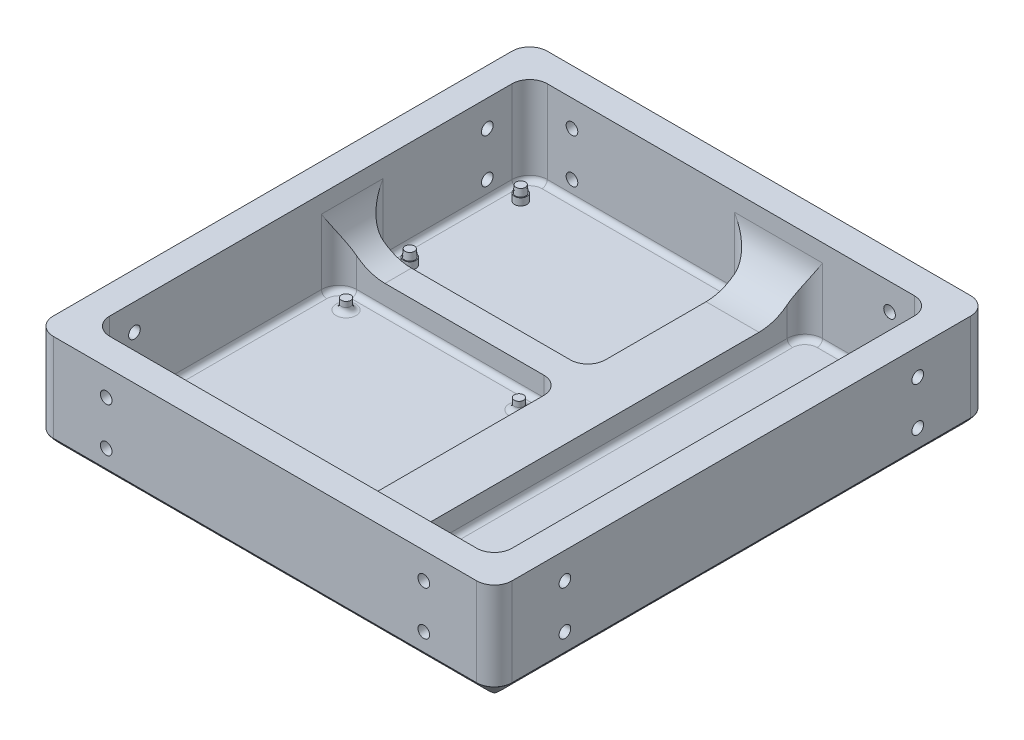
SolidWorks part; units mm, degrees
ref_plane "Front Plane" through (0, 0, 0) normal (0, 0, 1) x (1, 0, 0)
ref_plane "Top Plane" through (0, 0, 0) normal (0, 1, 0) x (1, 0, 0)
ref_plane "Right Plane" through (0, 0, 0) normal (1, 0, 0) x (0, 0, -1)
sketch "Sketch1" plane through (0, 0, 0) normal (0, 1, 0) x (1, 0, 0)
  line L1 (-83.6568, 40.258) -> (46.3432, 40.258)
  line L2 (-83.6568, 40.258) -> (-83.6568, -99.742)
  line L3 (-83.6568, -99.742) -> (46.3432, -99.742)
  line L4 (46.3432, 40.258) -> (46.3432, -99.742)
  dimension "D1" = 140
  dimension "D2" = 130
extrude "Boss-Extrude2" add sketch "Sketch1" along normal blind 10
sketch "Sketch3" plane through (0, 10, 0) normal (0, 1, 0) x (1, 0, 0)
  line L0 (-83.6568, -99.742) -> (46.3432, -99.742) construction
  line L1 (-83.6568, 40.258) -> (-83.6568, -99.742) construction
  circle A0 centre (-68.6568, -26.742) radius 1.3
  circle A1 centre (-19.6568, -26.742) radius 1.3
  circle A2 centre (-68.6568, -84.742) radius 1.3
  circle A3 centre (-19.6568, -84.742) radius 1.3
  dimension "D1" = 49
  dimension "D2" = 58
  dimension "D3" = 49
  dimension "D6" = 2.6
  dimension "D7" = 2.6
  dimension "D8" = 2.6
  dimension "D9" = 2.6
  dimension "D4" = 15
  dimension "D5" = 15
extrude "Boss-Extrude4" add sketch "Sketch3" along normal blind 2
sketch "Sketch4" plane through (0, 12, 0) normal (0, 1, 0) x (1, 0, 0)
  circle A0 centre (-68.6568, -26.742) radius 1.15
  circle A1 centre (-68.6568, -84.742) radius 1.15
  circle A2 centre (-19.6568, -84.742) radius 1.15
  circle A3 centre (-19.6568, -26.742) radius 1.15
  dimension "D1" = 2.3
  dimension "D2" = 2.3
  dimension "D3" = 2.3
  dimension "D4" = 2.3
extrude "Boss-Extrude5" add sketch "Sketch4" along normal blind 3 draft 5 draft outward yes
chamfer "Chamfer1" distance 1.5 angle 45 4 edges at (-19.6568, 15, 86.1545) (-68.6568, 15, 28.1545) (-19.6568, 15, 28.1545) (-68.6568, 15, 86.1545)
sketch "Sketch5" plane through (0, 10, 0) normal (0, 1, 0) x (1, 0, 0)
  line L0 (46.3432, 40.258) -> (-83.6568, 40.258) construction
  line L1 (-83.6568, -99.742) -> (-73.6568, -99.742)
  line L2 (-83.6568, -99.742) -> (-83.6568, 40.258)
  line L3 (-83.6568, 40.258) -> (-73.6568, 40.258)
  line L4 (-73.6568, -89.742) -> (-73.6568, 30.258)
  line L5 (46.3432, -99.742) -> (46.3432, 40.258) construction
  line L6 (46.3432, 40.258) -> (-83.6568, 40.258)
  line L7 (46.3432, 40.258) -> (46.3432, 30.258)
  line L8 (36.3432, 30.258) -> (-73.6568, 30.258)
  line L9 (-83.6568, 40.258) -> (-83.6568, 30.258)
  line L10 (-83.6568, -99.742) -> (46.3432, -99.742)
  line L11 (-83.6568, -99.742) -> (-83.6568, -89.742)
  line L12 (-73.6568, -89.742) -> (36.3432, -89.742)
  line L13 (46.3432, -99.742) -> (46.3432, -89.742)
  line L15 (46.3432, -99.742) -> (36.3432, -99.742)
  line L16 (46.3432, -99.742) -> (46.3432, 40.258)
  line L17 (46.3432, 40.258) -> (36.3432, 40.258)
  line L18 (36.3432, -89.742) -> (36.3432, 30.258)
  line M3 (-83.6568, 40.258) -> (-83.6568, -99.742)
  line M4 (-83.6568, -99.742) -> (46.3432, -99.742)
  line M5 (46.3432, -99.742) -> (46.3432, 40.258)
  line M6 (46.3432, 40.258) -> (-83.6568, 40.258)
  dimension "D1" = 10
  dimension "D2" = 10
  dimension "D3" = 10
  dimension "D4" = 10
extrude "Boss-Extrude6" add sketch "Sketch5" along normal blind 20 contours L6 L2 L10 L18 L12 L4 L8 M6 M3 M4 M5
sketch "Sketch7" plane through (0, 30, 0) normal (0, 1, 0) x (1, 0, 0)
  line L0 (46.3432, 40.258) -> (-83.6568, 40.258) construction
  line L1 (-75.6568, 32.258) -> (38.3432, 32.258)
  line L2 (-75.6568, 32.258) -> (-75.6568, -91.742)
  line L3 (-75.6568, -91.742) -> (38.3432, -91.742)
  line L4 (38.3432, 32.258) -> (38.3432, -91.742)
  line L5 (-83.6568, -99.742) -> (46.3432, -99.742) construction
  line L6 (-83.6568, 40.258) -> (-83.6568, -99.742) construction
  line L7 (46.3432, -99.742) -> (46.3432, 40.258) construction
  line L9 (-73.6568, 30.258) -> (36.3432, 30.258)
  line L10 (-73.6568, 30.258) -> (-73.6568, -89.742)
  line L11 (-73.6568, -89.742) -> (36.3432, -89.742)
  line L12 (36.3432, 30.258) -> (36.3432, -89.742)
  dimension "D1" = 8
  dimension "D2" = 8
  dimension "D3" = 8
  dimension "D4" = 8
extrude "Cut-Extrude2" cut sketch "Sketch7" against normal up to surface (20 mm away) up to face at (-18.6568, 10, 29.742)
sketch "Sketch9" plane through (0, 10, 0) normal (0, 1, 0) x (1, 0, 0)
  line L0 (38.3432, -91.742) -> (-75.6568, -91.742) construction
  line L1 (-12.6568, -91.742) -> (2.3432, -91.742)
  line L2 (-12.6568, -91.742) -> (-12.6568, 32.258)
  line L3 (-12.6568, 32.258) -> (2.3432, 32.258)
  line L4 (2.3432, -91.742) -> (2.3432, 32.258)
  line L5 (38.3432, -91.742) -> (38.3432, 32.258) construction
  line L6 (-75.6568, 32.258) -> (38.3432, 32.258) construction
  dimension "D1" = 15
  dimension "D2" = 36
  dimension "D3" = 0
extrude "Boss-Extrude8" add sketch "Sketch9" along normal blind 5
sketch "Sketch10" plane through (0, 10, 0) normal (0, 1, 0) x (1, 0, 0)
  line L0 (-75.6568, -91.742) -> (-75.6568, 32.258) construction
  line L1 (-75.6568, -21.742) -> (-12.6568, -21.742)
  line L2 (-75.6568, -21.742) -> (-75.6568, -14.242)
  line L3 (-75.6568, -14.242) -> (-12.6568, -14.242)
  line L4 (-12.6568, -21.742) -> (-12.6568, -14.242)
  line L5 (-12.6568, 32.258) -> (-12.6568, -91.742) construction
  circle A0 centre (-68.6568, -26.742) radius 1.2817 construction
  dimension "D1" = 7.5
  dimension "D2" = 5
extrude "Boss-Extrude9" add sketch "Sketch10" along normal blind 5
sketch "Sketch12" plane through (0, 10, 0) normal (0, 1, 0) x (1, 0, 0)
  line L1 (-75.6568, 32.258) -> (-12.6568, 32.258)
  line L2 (-75.6568, 32.258) -> (-75.6568, -14.242)
  line L3 (-75.6568, -14.242) -> (-12.6568, -14.242)
  line L4 (-12.6568, 32.258) -> (-12.6568, -14.242)
  line L5 (2.3432, 32.258) -> (38.3432, 32.258)
  line L6 (2.3432, 32.258) -> (2.3432, -91.742)
  line L7 (2.3432, -91.742) -> (38.3432, -91.742)
  line L8 (38.3432, 32.258) -> (38.3432, -91.742)
  line L9 (-12.6568, -91.742) -> (-75.6568, -91.742)
  line L10 (-12.6568, -91.742) -> (-12.6568, -21.742)
  line L11 (-12.6568, -21.742) -> (-75.6568, -21.742)
  line L12 (-75.6568, -91.742) -> (-75.6568, -21.742)
  circle A0 centre (-68.6846, -26.742) radius 1.3279
  circle A1 centre (-68.6568, -26.742) radius 0.0279 construction
  circle A2 centre (-19.6568, -26.7699) radius 1.3279
  circle A3 centre (-19.6568, -26.742) radius 0.0279 construction
  circle A4 centre (-19.6289, -84.742) radius 1.2539
  circle A5 centre (-19.6568, -84.742) radius 0.0279 construction
  circle A6 centre (-68.6568, -84.7141) radius 1.2539
  circle A7 centre (-68.6568, -84.742) radius 0.0279 construction
extrude "Cut-Extrude6" cut sketch "Sketch12" against normal blind 5
sketch "Sketch14" plane through (0, 15, 0) normal (0, 1, 0) x (1, 0, 0)
  line L1 (-75.6568, -21.742) -> (-15.6932, -21.742)
  line L2 (-75.6568, -21.742) -> (-75.6568, -90.2178)
  line L3 (-75.6568, -90.2178) -> (-15.6932, -90.2178)
  line L4 (-15.6932, -21.742) -> (-15.6932, -90.2178)
extrude "Cut-Extrude9" cut sketch "Sketch14" against normal blind 7
sketch "Sketch16" plane through (0, 15, 0) normal (0, 1, 0) x (1, 0, 0)
  line L1 (-75.6568, 32.258) -> (38.3432, 32.258)
  line L2 (-75.6568, 32.258) -> (-75.6568, -91.742)
  line L3 (-75.6568, -91.742) -> (38.3432, -91.742)
  line L4 (38.3432, 32.258) -> (38.3432, -91.742)
extrude "Cut-Extrude10" cut sketch "Sketch16" against normal blind 3
fillet "Fillet12" radius 13 3 edges at (-5.1568, 12, 91.742) (-5.1568, 12, -32.258) (-75.6568, 12, 17.992)
fillet "Fillet13" radius 5 12 edges at (2.3432, 15, 91.742) (-75.6568, 15, 21.742) (-12.6568, 8.5, 21.742) (-75.6568, 17.5, 91.742) (38.3432, 17.5, -32.258) (-12.6568, 15, 91.742) (38.3432, 17.5, 91.742) (2.3432, 15, -32.258) (-75.6568, 15, 14.242) (-12.6568, 8.5, 14.242) (-12.6568, 15, -32.258) (-75.6568, 17.5, -32.258)
fillet "Fillet14" radius 5 4 edges at (46.3432, 15, 99.742) (46.3432, 15, -40.258) (-83.6568, 15, -40.258) (-83.6568, 15, 99.742)
fillet "Fillet15" radius 1.5 28 edges at (3.8077, 5, -30.7935) (20.3432, 5, -32.258) (36.8788, 5, -30.7935) (38.3432, 5, 29.742) (36.8788, 5, 90.2775) (20.3432, 5, 91.742) (3.8077, 5, 90.2775) (2.3432, 5, 29.742) (-74.1923, 5, -30.7935) (-44.1568, 5, -32.258) (-14.1212, 5, -30.7935) (-12.6568, 5, -9.008) (-14.1212, 5, 12.7775) (-44.1568, 5, 14.242) (-74.1923, 5, 12.7775) (-75.6568, 5, -9.008) (-14.1212, 5, 23.2065) (-12.6568, 5, 56.742) (-14.1212, 5, 90.2775) (-44.1568, 5, 91.742) (-74.1923, 5, 90.2775) (-75.6568, 5, 56.742) (-74.1923, 5, 23.2065) (-44.1568, 5, 21.742) (-68.6846, 5, 28.0699) (-19.6568, 5, 28.0977) (-19.6289, 5, 85.9958) (-68.6568, 5, 85.968)
sketch "Sketch24" plane through (46.3432, 0, 0) normal (1, 0, 0) x (0, 0, -1)
  line L0 (-94.742, 0) -> (35.258, 0) construction
  line L2 (40.258, 30) -> (40.258, 0) construction
  circle A0 centre (-79.742, 22.5) radius 1.65
  circle A1 centre (-79.742, 10) radius 1.65
  circle A2 centre (20.258, 22.5) radius 1.65
  circle A3 centre (20.258, 10) radius 1.65
  dimension "D1" = 12.5
  dimension "D5" = 20
  dimension "D6" = 12.5
  dimension "D2" = 10
  dimension "D3" = 20
  dimension "D4" = 20
  dimension "D7" = 10
extrude "Cut-Extrude16" cut sketch "Sketch24" against normal blind 10
sketch "Sketch25" plane through (-83.6568, 0, 0) normal (-1, 0, 0) x (0, 0, 1)
  line L0 (-40.258, 0) -> (-40.258, 30) construction
  line L1 (-35.258, 0) -> (94.742, 0) construction
  line L2 (99.742, 30) -> (99.742, 0) construction
  circle A0 centre (-20.258, 22.5) radius 1.65
  circle A1 centre (-20.258, 10) radius 1.65
  circle A2 centre (79.742, 10) radius 1.65
  circle A3 centre (79.742, 22.5) radius 1.65
  dimension "D1" = 20
  dimension "D3" = 10
  dimension "D4" = 20
  dimension "D2" = 22.5
extrude "Cut-Extrude17" cut sketch "Sketch25" against normal blind 10
sketch "Sketch26" plane through (0, 0, 99.742) normal (0, 0, 1) x (1, 0, 0)
  line L0 (-83.6568, 0) -> (-83.6568, 30) construction
  line L1 (-78.6568, 0) -> (41.3432, 0) construction
  line L2 (46.3432, 30) -> (46.3432, 0) construction
  circle A0 centre (-63.6568, 22.5) radius 1.65
  circle A1 centre (-63.6568, 10) radius 1.65
  circle A2 centre (26.3432, 10) radius 1.65
  circle A3 centre (26.3432, 22.5) radius 1.65
  dimension "D1" = 20
  dimension "D3" = 12.5
  dimension "D4" = 20
  dimension "D2" = 22.5
extrude "Cut-Extrude18" cut sketch "Sketch26" against normal blind 10
sketch "Sketch27" plane through (0, 0, -40.258) normal (0, 0, -1) x (-1, 0, 0)
  line L0 (-46.3432, 0) -> (-46.3432, 30) construction
  line L2 (-41.3432, 0) -> (78.6568, 0) construction
  line L3 (83.6568, 30) -> (83.6568, 0) construction
  circle A0 centre (-26.3432, 22.5) radius 1.65
  circle A1 centre (-26.3432, 10) radius 1.65
  circle A2 centre (63.6568, 22.5) radius 1.65
  circle A3 centre (63.6568, 10) radius 1.65
  point P10 (83.6568, 15)
  dimension "D1" = 20
  dimension "D3" = 12.5
  dimension "D4" = 20
  dimension "D2" = 22.5
extrude "Cut-Extrude19" cut sketch "Sketch27" against normal blind 10
fillet "Fillet17" radius 5 8 edges at (44.8788, 0, -38.7935) (-18.6568, 0, -40.258) (-82.1923, 0, -38.7935) (-83.6568, 0, 29.742) (-82.1923, 0, 98.2775) (-18.6568, 0, 99.742) (44.8788, 0, 98.2775) (46.3432, 0, 29.742)
sketch "Sketch30" plane through (0, 5, 0) normal (0, 1, 0) x (1, 0, 0)
  line L0 (-75.6568, -9.242) -> (-75.6568, 27.258) construction
  line L1 (-17.6568, -14.242) -> (-70.6568, -14.242) construction
  circle A0 centre (-70.6568, 24.723) radius 1.75
  circle A1 centre (-70.6568, -6.707) radius 1.75
  dimension "D1" = 5
  dimension "D2" = 3.5
  dimension "3.5" = 3.5
  dimension "D3" = 31.43
  dimension "D4" = 7.535
extrude "Boss-Extrude10" add sketch "Sketch30" along normal blind 2
sketch "Sketch31" plane through (0, 7, 0) normal (0, 1, 0) x (1, 0, 0)
  circle A0 centre (-70.6568, 24.723) radius 1.5
  circle A1 centre (-70.6568, -6.707) radius 1.5
extrude "Boss-Extrude11" add sketch "Sketch31" along normal blind 2 draft 5
